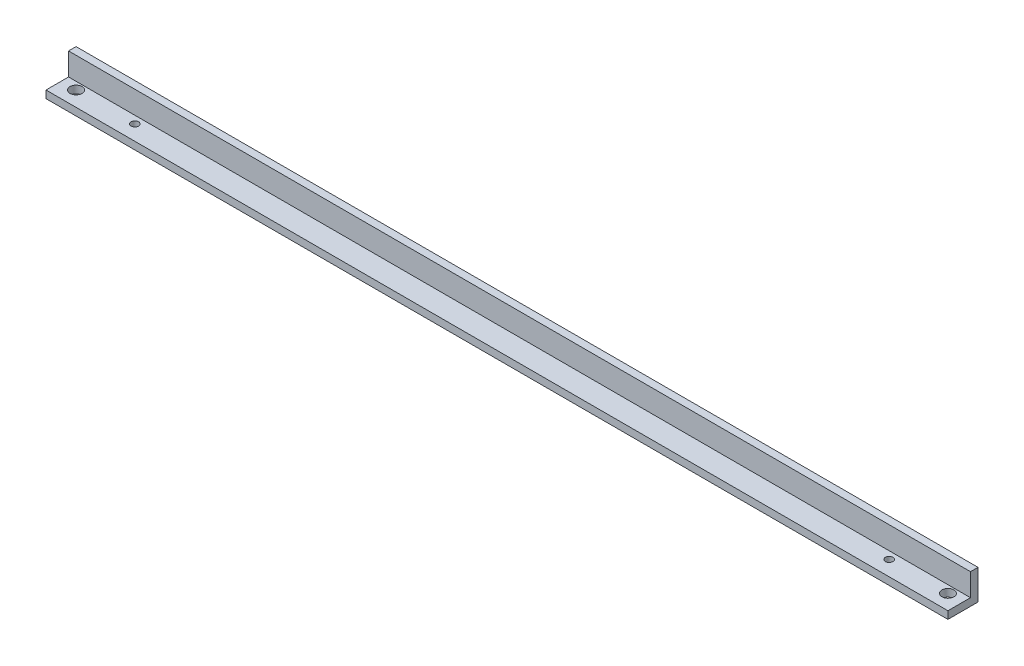
SolidWorks part; units mm, degrees
material "6061-T6 (SS)"
ref_plane "Front Plane" through (0, 0, 0) normal (0, 0, 1) x (1, 0, 0)
ref_plane "Top Plane" through (0, 0, 0) normal (0, 1, 0) x (1, 0, 0)
ref_plane "Right Plane" through (0, 0, 0) normal (1, 0, 0) x (0, 0, -1)
sketch "Sketch1" plane through (0, 0, 0) normal (1, 0, 0) x (0, 0, -1)
  line L0 (0, 0) -> (0, 19.05)
  line L1 (0, 19.05) -> (6.35, 19.05)
  line L2 (6.35, 19.05) -> (6.35, -6.35)
  line L3 (6.35, -6.35) -> (-19.05, -6.35)
  line L4 (-19.05, -6.35) -> (-19.05, 0)
  line L5 (-19.05, 0) -> (0, 0)
  dimension "D1" = 25.4
  dimension "D2" = 25.4
  dimension "D3" = 6.35
  dimension "D4" = 6.35
extrude "Boss-Extrude1" add sketch "Sketch1" along normal blind 762
sketch "Sketch2" plane through (0, -6.35, 0) normal (0, -1, 0) x (1, 0, 0)
  line L0 (0, 6.35) -> (762, 6.35) construction
  line L1 (0, 19.05) -> (0, -6.35) construction
  line L2 (381, 19.05) -> (381, -6.35) construction
  line L5 (762, 19.05) -> (762, -6.35) construction
  line L6 (762, 19.05) -> (0, 19.05) construction
  line L7 (762, -6.35) -> (0, -6.35) construction
  circle A0 centre (12.7, 6.35) radius 5.08
  circle A1 centre (62.357, 6.35) radius 3.175
  circle A8 centre (699.643, 6.35) radius 3.175
  circle A9 centre (749.3, 6.35) radius 5.08
  dimension "D1" = 10.16
  dimension "D2" = 6.35
  dimension "D3" = 12.7
  dimension "D4" = 49.657
extrude "Cut-Extrude1" cut sketch "Sketch2" against normal blind 914.4
